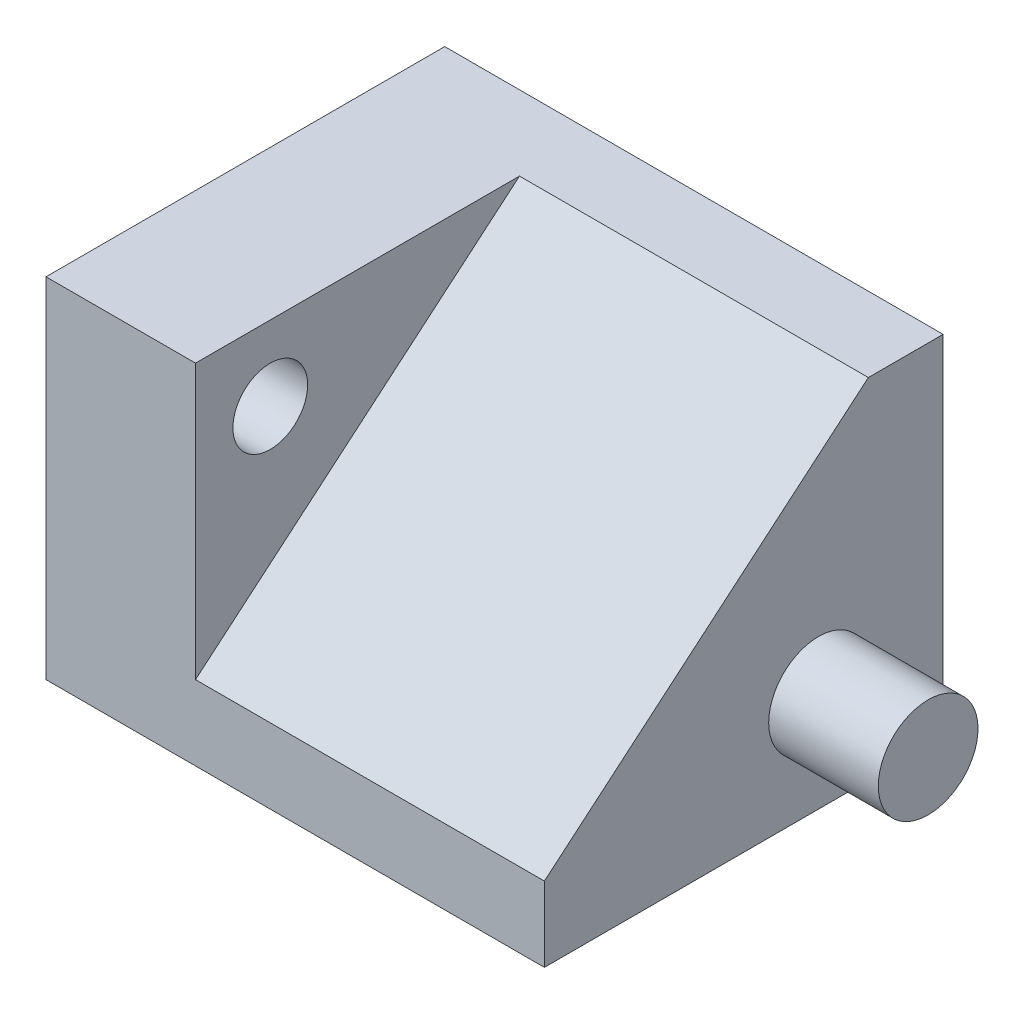
SolidWorks part; units mm, degrees
ref_plane "Front Plane" through (0, 0, 0) normal (0, 0, 1) x (1, 0, 0)
ref_plane "Top Plane" through (0, 0, 0) normal (0, 1, 0) x (1, 0, 0)
ref_plane "Right Plane" through (0, 0, 0) normal (1, 0, 0) x (0, 0, -1)
sketch "Sketch1" plane through (0, 0, 0) normal (0, 1, 0) x (1, 0, 0)
  line L0 (0, 82.55) -> (-88.9, 82.55)
  line L1 (0, 0) -> (-127, 0)
  line L2 (0, 0) -> (0, 101.6)
  line L3 (0, 101.6) -> (-127, 101.6)
  line L4 (-127, 0) -> (-127, 101.6)
  line L5 (-127, 101.6) -> (0, 101.6)
  line L6 (-127, 101.6) -> (-127, 82.55)
  line L8 (0, 101.6) -> (0, 82.55)
  line L9 (-127, 0) -> (-88.9, 0)
  line L10 (-127, 0) -> (-127, 82.55)
  line L12 (-88.9, 0) -> (-88.9, 82.55)
  line L13 (-88.9, 0) -> (-88.9, 82.55)
  dimension "D1" = 127
  dimension "D2" = 101.6
  dimension "D3" = 19.05
  dimension "D4" = 38.1
extrude "Boss-Extrude1" add sketch "Sketch1" along normal blind 19.05 contours L12 L1 L2 L0 region at (-44.45, 0, -41.275)
extrude "Boss-Extrude2" add sketch "Sketch1<3>" along normal blind 88.9 contours L1 L12 L0 L2 L3 L4 region at (-44.45, 0, -84.1764)
sketch "Sketch1<3>" plane through (0, 0, 0) normal (0, 1, 0) x (1, 0, 0) same geometry as "Sketch1"
sketch "Sketch2" plane through (-88.9, 0, 0) normal (1, 0, 0) x (0, 0, -1)
  line L0 (0, 19.05) -> (82.55, 88.9)
  line L1 (0, 19.05) -> (82.55, 19.05)
  line L2 (82.55, 19.05) -> (82.55, 88.9)
extrude "Boss-Extrude3" add sketch "Sketch2" along normal blind 88.9
sketch "Sketch5" plane through (-88.9, 0, 0) normal (1, 0, 0) x (0, 0, -1)
  line L0 (0, 88.9) -> (0, 19.05) construction
  line L1 (0, 88.9) -> (82.55, 88.9) construction
  circle A0 centre (19.05, 69.85) radius 9.525
  dimension "D1" = 19.05
  dimension "D2" = 19.05
  dimension "D3" = 19.05
extrude "Cut-Extrude1" cut sketch "Sketch5" against normal blind 88.9
sketch "Sketch6" plane through (0, 0, 0) normal (1, 0, 0) x (0, 0, -1)
  line L0 (101.6, 88.9) -> (101.6, 0) construction
  line L1 (0, 0) -> (101.6, 0) construction
  circle A0 centre (69.85, 25.4) radius 12.7
  point P4 (0, 0)
  point P6 (19.8245, 95.8877)
  dimension "D1" = 25.4
  dimension "D2" = 31.75
  dimension "D3" = 25.4
extrude "Boss-Extrude4" add sketch "Sketch6" along normal blind 27.94
